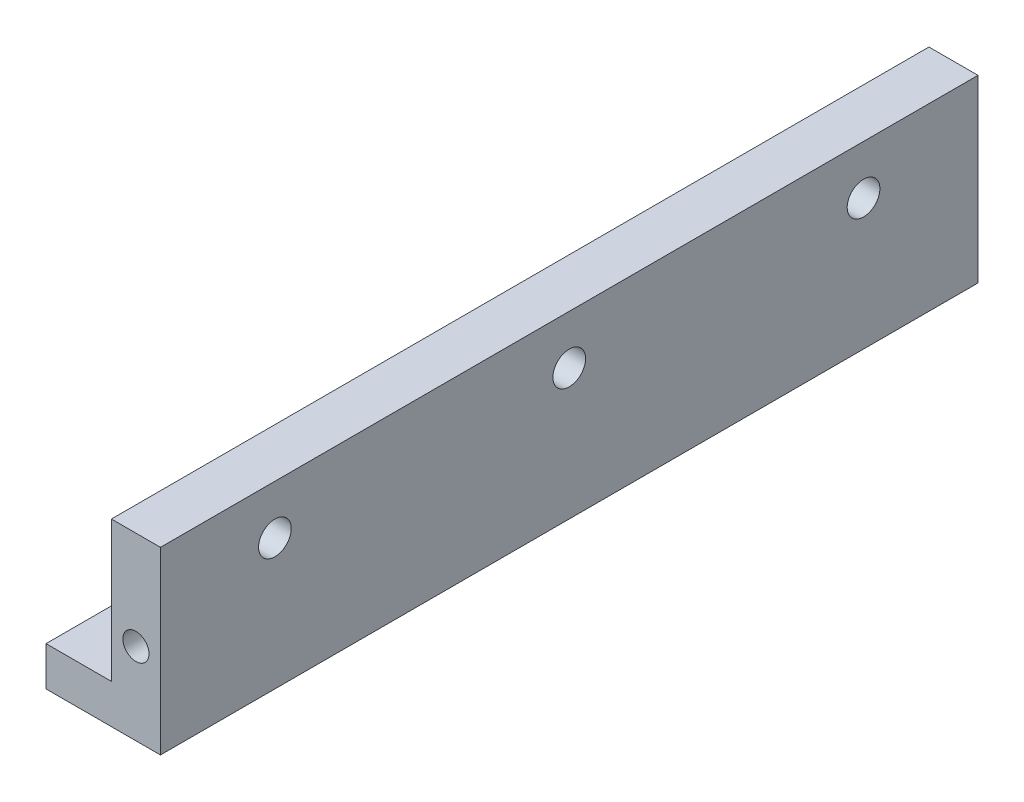
SolidWorks part; units mm, degrees
ref_plane "前基準面" through (0, 0, 0) normal (0, 0, 1) x (1, 0, 0)
ref_plane "上基準面" through (0, 0, 0) normal (0, 1, 0) x (1, 0, 0)
ref_plane "右基準面" through (0, 0, 0) normal (1, 0, 0) x (0, 0, -1)
sketch "草圖1" plane through (0, 0, 0) normal (0, 0, 1) x (1, 0, 0)
  line L0 (-5.0196, 208.8052) -> (-5.0196, 165.8052)
  line L2 (-5.0196, 165.8052) -> (-25.0196, 165.8052)
  line L3 (-25.0196, 165.8052) -> (-25.0196, 153.8052)
  line L4 (-25.0196, 153.8052) -> (9.9804, 153.8052)
  line L5 (9.9804, 153.8052) -> (9.9804, 208.8052)
  line L6 (9.9804, 208.8052) -> (-5.0196, 208.8052)
  circle A0 centre (2.4804, 178.8052) radius 4
  dimension "D5" = 8
  dimension "D7" = 30
  dimension "D1" = 35
  dimension "D2" = 12
  dimension "D3" = 55
  dimension "D4" = 15
  dimension "D6" = 7.5
extrude "填料-伸長1" add sketch "草圖1" against normal up to surface (250 mm away)
sketch "草圖2" plane through (9.9804, 0, 0) normal (1, 0, 0) x (0, 0, -1)
  line L0 (0, 153.8052) -> (0, 208.8052) construction
  line L1 (250, 208.8052) -> (0, 208.8052) construction
  circle A0 centre (35, 193.8052) radius 5
  circle A1 centre (125, 193.8052) radius 5
  circle A2 centre (215, 193.8052) radius 5
  dimension "D1" = 10
  dimension "D2" = 10
  dimension "D3" = 10
  dimension "D7" = 15
  dimension "D4" = 90
  dimension "D5" = 90
  dimension "D6" = 35
extrude "除料-伸長1" cut sketch "草圖2" against normal up to next and the other way through all
